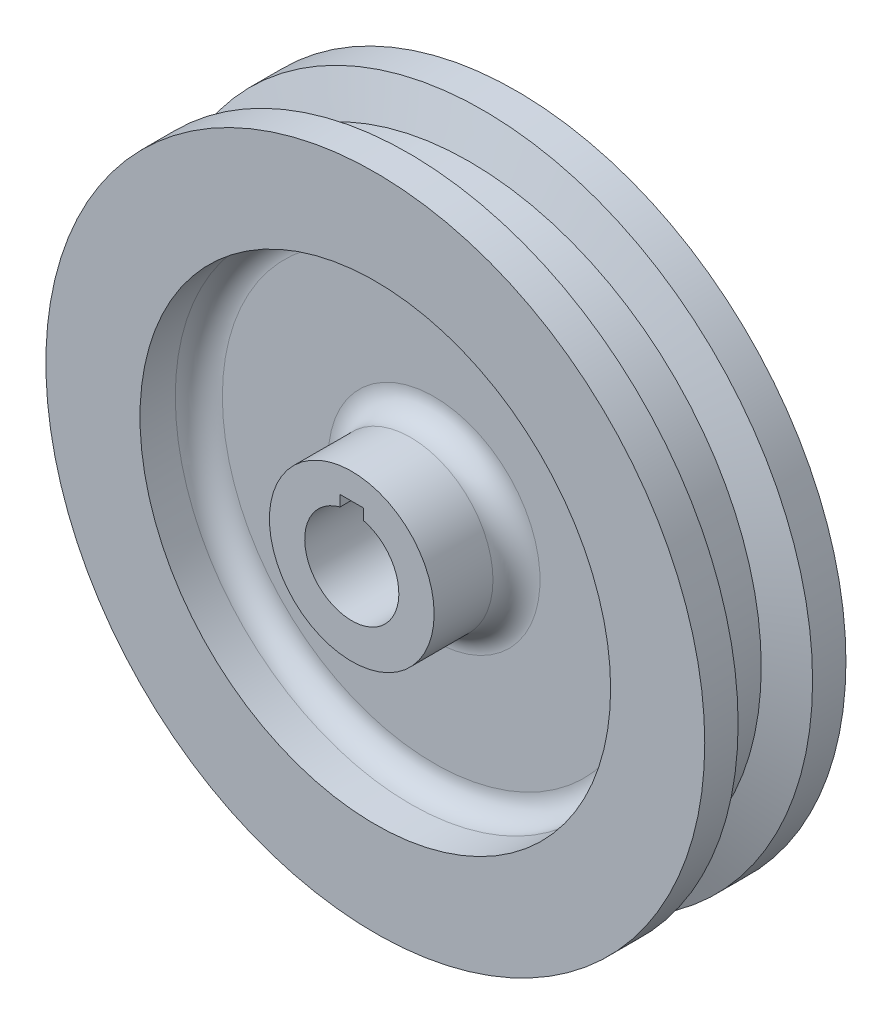
SolidWorks part; units mm, degrees
material "Cast Carbon Steel"
ref_plane "Front Plane" through (0, 0, 0) normal (0, 0, 1) x (1, 0, 0)
ref_plane "Top Plane" through (0, 0, 0) normal (0, 1, 0) x (1, 0, 0)
ref_plane "Right Plane" through (0, 0, 0) normal (1, 0, 0) x (0, 0, -1)
sketch "Sketch1" plane through (0, 0, 0) normal (1, 0, 0) x (0, 0, -1)
  line L0 (0, 0) -> (0, 130.3734) construction
  line L1 (0, 0) -> (71.4556, 0) construction
  line L2 (-25.4, 12.7) -> (25.4, 12.7)
  line L3 (-25.4, 12.7) -> (-25.4, 22.225)
  line L4 (-25.4, 22.225) -> (-3.175, 22.225)
  line L5 (25.4, 12.7) -> (25.4, 22.225)
  line L6 (-25.4, 12.7) -> (25.4, 22.225) construction
  line L7 (-25.4, 22.225) -> (25.4, 12.7) construction
  line L8 (-19.05, 88.9) -> (19.05, 88.9)
  line L9 (-19.05, 88.9) -> (-19.05, 63.5)
  line L10 (-19.05, 63.5) -> (-3.175, 63.5)
  line L11 (19.05, 88.9) -> (19.05, 63.5)
  line L12 (-19.05, 88.9) -> (19.05, 63.5) construction
  line L13 (-19.05, 63.5) -> (19.05, 88.9) construction
  line L19 (-3.175, 22.225) -> (-3.175, 63.5)
  line L21 (3.175, 22.225) -> (3.175, 63.5)
  line L22 (3.175, 63.5) -> (19.05, 63.5)
  line L23 (3.175, 22.225) -> (25.4, 22.225)
  point P3 (0, 17.4625)
  point P8 (0, 76.2)
  dimension "D1" = 38.1
  dimension "D2" = 50.8
  dimension "D3" = 25.4
  dimension "D4" = 6.35
  dimension "D5" = 44.45
  dimension "D6" = 127
  dimension "D7" = 177.8
revolve "Revolve2" add sketch "Sketch1" angle 360 about L1
sketch "Sketch2" plane through (0, 0, 0) normal (1, 0, 0) x (0, 0, -1)
  line L0 (0, 88.9) -> (0, 72.999) construction
  line L1 (19.05, 88.9) -> (-19.05, 88.9) construction
  line L2 (-10.0479, 88.9) -> (-6.35, 78.74)
  line L3 (-6.35, 78.74) -> (6.35, 78.74)
  line L4 (6.35, 78.74) -> (10.0479, 88.9)
  line L6 (0, 0) -> (87.7987, 0) construction
  line L7 (-10.0479, 88.9) -> (10.0479, 88.9)
  dimension "D1" = 40
  dimension "D2" = 10.16
  dimension "D3" = 12.7
revolve "Cut-Revolve1" cut sketch "Sketch2" angle 360 about L6
fillet "Fillet1" radius 6.35 4 edges at (63.5, 0, -3.175) (22.225, 0, -3.175) (22.225, 0, 3.175) (63.5, 0, 3.175)
sketch "Sketch3" plane through (0, 0, 25.4) normal (0, 0, 1) x (1, 0, 0)
  line L0 (-3.175, 0) -> (3.175, 0)
  line L1 (-3.175, 0) -> (-3.175, 15.24)
  line L2 (3.175, 0) -> (3.175, 15.24)
  line L3 (-3.175, 15.24) -> (3.175, 15.24)
  point P0 (0, 0)
  dimension "D1" = 15.24
  dimension "D2" = 6.35
extrude "Cut-Extrude1" cut sketch "Sketch3" against normal through all
